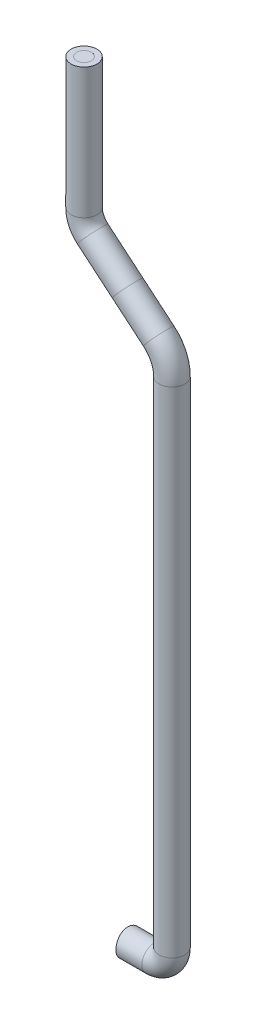
SolidWorks part; units mm, degrees
material "Изоляция провода синяя"
ref_plane "Спереди" through (0, 0, 0) normal (0, 0, 1) x (1, 0, 0)
ref_plane "Сверху" through (0, 0, 0) normal (0, 1, 0) x (1, 0, 0)
ref_plane "Справа" through (0, 0, 0) normal (1, 0, 0) x (0, 0, -1)
sketch "Эскиз1" plane through (0, 0, 0) normal (0, 1, 0) x (1, 0, 0)
  circle A0 centre (0, 0) radius 1.05
  dimension "D1" = 2.1
sketch "Эскиз2" plane through (0, 0, 0) normal (0, 0, 1) x (1, 0, 0)
  line L0 (0, 0) -> (0, 50000) construction
  line L1 (1.05, 0) -> (-1.05, 0) construction
  line L2 (-3.6, 0.6487) -> (-3.6, 50000.6487) construction
  line L3 (0, 0) -> (0, 40.1803)
  line L4 (-1.0716, 42.4785) -> (-3.6, 44.6)
  line L5 (-3.6, 44.6) -> (-6.4356, 46.9793)
  line L6 (-6.1, 36.9798) -> (-6.1, 50036.9798) construction
  line L7 (-7.15, 48.5114) -> (-7.15, 59.1195)
  arc A0 (0, 40.1803) -> (-1.0716, 42.4785) centre (-3, 40.1803) ccw
  arc A1 (-6.4356, 46.9793) -> (-7.15, 48.5114) centre (-5.15, 48.5114) cw
  point P4 (0, 0)
  point P13 (0, 41.5792)
  dimension "D5" = 3
  dimension "D3" = 2
  dimension "D1" = 3.6
  dimension "D2" = 41.5792
  dimension "D4" = 50
  dimension "D6" = 2.5
  dimension "D7" = 1.05
  dimension "D8" = 10.6081
sweep "По траектории1" add profiles "Эскиз1" path "Эскиз2"
sketch "Эскиз3" plane through (0, 0, 0) normal (0, -1, 0) x (1, 0, 0)
  circle A0 centre (0, 0) radius 0.6
  dimension "D1" = 1.2
sweep "Вырез-По траектории1" cut profiles "Эскиз3" path "Эскиз2<2>"
sketch "Эскиз2<2>" plane through (0, 0, 0) normal (0, 0, 1) x (1, 0, 0) same geometry as "Эскиз2"
sketch "Эскиз4" plane through (0, 0, 0) normal (0, -1, 0) x (1, 0, 0)
  circle A0 centre (0, 0) radius 0.6 construction
  circle A1 centre (0, 0) radius 0.6
sweep "По траектории2" add profiles "Эскиз4" path "Эскиз2<3>"
sketch "Эскиз2<3>" plane through (0, 0, 0) normal (0, 0, 1) x (1, 0, 0) same geometry as "Эскиз2"
sketch "Эскиз5" plane through (0, 0, 0) normal (0, 0, 1) x (1, 0, 0)
  line L0 (0, 0) -> (0, -50000) construction
  line L1 (0, -1.4) -> (-50000, -1.4) construction
  line L2 (-1.05, 0) -> (1.05, 0) construction
  line L3 (-1.4, -1.4) -> (-3.6, -1.4)
  arc A0 (0, 0) -> (-1.4, -1.4) centre (-1.4, 0) cw
  dimension "D1" = 1.4
  dimension "D2" = 3.6
sketch "Эскиз6" plane through (0, 0, 0) normal (0, -1, 0) x (1, 0, 0)
  circle A1 centre (0, 0) radius 0.6
  circle A2 centre (0, 0) radius 0.6
  dimension "D1" = 0
sweep "По траектории3" add profiles "Эскиз6" path "Эскиз5"
sketch "Эскиз7" plane through (0, 0, 0) normal (0, -1, 0) x (1, 0, 0)
  circle A0 centre (0, 0) radius 0.6 construction
  circle A1 centre (0, 0) radius 1.05
  circle A2 centre (0, 0) radius 1.05
  circle A3 centre (0, 0) radius 0.6
  dimension "D1" = 0
sweep "По траектории4" add profiles "Эскиз7" path "Эскиз5<2>"
sketch "Эскиз5<2>" plane through (0, 0, 0) normal (0, 0, 1) x (1, 0, 0) same geometry as "Эскиз5"
ref_plane "Плоскость1" through (0, -2.45, 0) normal (0, -1, 0) x (-1, 0, 0)
sketch "Эскиз8" plane through (0, -2.45, 0) normal (0, -1, 0) x (-1, 0, 0)
  line L0 (3.6, -1.05) -> (3.6, 1.05) construction
  line L1 (3.6, -1.05) -> (3.6, 1.05)
  line L2 (0, 0) -> (-50000, 0) construction
  line L3 (3.6, 1.05) -> (3.5074, 1.05)
  line L5 (3.6, -1.05) -> (3.5074, -1.05)
  arc A0 (3.5074, -1.05) -> (3.5074, 1.05) centre (-2.4, 0) ccw
  dimension "D1" = 12
extrude "Вырез-Вытянуть1" cut sketch "Эскиз8" against normal blind 10 contours A0 L1 L3 region at (-3.5723, -2.45, -0.7879)
extrude "Вырез-Вытянуть2" cut sketch "Эскиз8<3>" against normal blind 10 contours A0 L5 L1 region at (-3.5723, -2.45, 0.7879)
sketch "Эскиз8<3>" plane through (0, -2.45, 0) normal (0, -1, 0) x (-1, 0, 0) same geometry as "Эскиз8"
